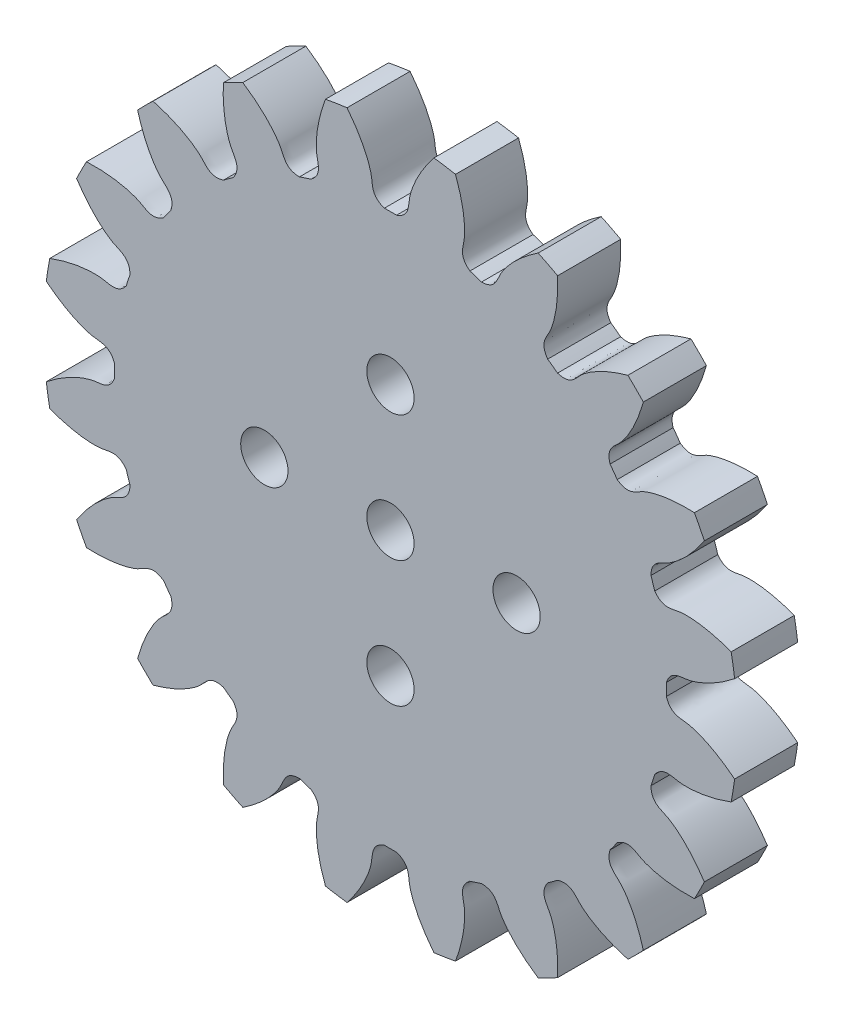
SolidWorks part; units mm, degrees
material "Thornel Mat VMA"
ref_plane "前视基准面" through (0, 0, 0) normal (0, 0, 1) x (1, 0, 0)
ref_plane "上视基准面" through (0, 0, 0) normal (0, 1, 0) x (1, 0, 0)
ref_plane "右视基准面" through (0, 0, 0) normal (1, 0, 0) x (0, 0, -1)
other "Configuration Table"
sketch "草图1" plane through (0, 0, 0) normal (0, 0, 1) x (1, 0, 0)
  circle A0 centre (0, 0) radius 22
extrude "凸台-拉伸1" add sketch "草图1" along normal blind 4
ref_axis "基准轴1" through (0, 0, -1.5) along (0, 0, 1)
sketch "草图2" plane through (0, 0, 0) normal (0, 0, 1) x (1, 0, 0)
  line L0 (0, 0) -> (0, 22) construction
  circle A0 centre (0, 0) radius 22 construction
  arc A1 (0.3866, 17.4957) -> (-0.3866, 17.4957) centre (0, 0) ccw
  arc A2 (6.3623, 24.9965) -> (-6.3623, 24.9965) centre (0, 0) ccw
  spline S0 degree 3 poles (0.3866, 17.4957) (1.2224, 17.787) (1.1142, 18.3742) (1.2258, 18.94) (1.2378, 18.9951) (1.2526, 19.0573) (1.2706, 19.1264) (1.292, 19.2024) (1.317, 19.2851) (1.3461, 19.3745) (1.3793, 19.4704) (1.4171, 19.5726) (1.4597, 19.6811) (1.5073, 19.7956) (1.5603, 19.9161) (1.6187, 20.0423) (1.683, 20.174) (1.7534, 20.3112) (1.83, 20.4535) (1.9132, 20.6008) (2.0031, 20.7529) (2.1, 20.9095) (2.204, 21.0705) (2.3155, 21.2356) (2.4346, 21.4046) (2.5615, 21.5772) (2.6964, 21.7533) (2.8395, 21.9324) (2.991, 22.1145) (3.1509, 22.2992) (3.3196, 22.4862) (3.4971, 22.6753) (3.6837, 22.8662) (3.8793, 23.0586) (4.0843, 23.2521) (4.2986, 23.4467) (4.5225, 23.6418) (4.7559, 23.8372) (4.9991, 24.0327) (5.2521, 24.2278) (5.515, 24.4223) (5.8829, 24.6833) (6.1679, 24.8727) (6.3623, 24.9965) knots 0 0 0 0 0.165916 0.170906 0.176664 0.183189 0.190482 0.198542 0.207371 0.216967 0.22733 0.238462 0.250361 0.263027 0.276462 0.290664 0.305634 0.321371 0.337876 0.355149 0.37319 0.391998 0.411574 0.431917 0.453028 0.474907 0.497554 0.520968 0.54515 0.570099 0.595817 0.622302 0.649554 0.677575 0.706363 0.735918 0.766242 0.797333 0.829191 0.861818 0.895212 0.929373 1 1 1 1
  spline S1 degree 3 poles (-0.3866, 17.4957) (-1.2224, 17.787) (-1.1142, 18.3742) (-1.2258, 18.94) (-1.2378, 18.9951) (-1.2526, 19.0573) (-1.2706, 19.1264) (-1.292, 19.2024) (-1.317, 19.2851) (-1.3461, 19.3745) (-1.3793, 19.4704) (-1.4171, 19.5726) (-1.4597, 19.6811) (-1.5073, 19.7956) (-1.5603, 19.9161) (-1.6187, 20.0423) (-1.683, 20.174) (-1.7534, 20.3112) (-1.83, 20.4535) (-1.9132, 20.6008) (-2.0031, 20.7529) (-2.1, 20.9095) (-2.204, 21.0705) (-2.3155, 21.2356) (-2.4346, 21.4046) (-2.5615, 21.5772) (-2.6964, 21.7533) (-2.8395, 21.9324) (-2.991, 22.1145) (-3.1509, 22.2992) (-3.3196, 22.4862) (-3.4971, 22.6753) (-3.6837, 22.8662) (-3.8793, 23.0586) (-4.0843, 23.2521) (-4.2986, 23.4467) (-4.5225, 23.6418) (-4.7559, 23.8372) (-4.9991, 24.0327) (-5.2521, 24.2278) (-5.515, 24.4223) (-5.8829, 24.6833) (-6.1679, 24.8727) (-6.3623, 24.9965) knots 0 0 0 0 0.165916 0.170906 0.176664 0.183189 0.190482 0.198542 0.207371 0.216967 0.22733 0.238462 0.250361 0.263027 0.276462 0.290664 0.305634 0.321371 0.337876 0.355149 0.37319 0.391998 0.411574 0.431917 0.453028 0.474907 0.497554 0.520968 0.54515 0.570099 0.595817 0.622302 0.649554 0.677575 0.706363 0.735918 0.766242 0.797333 0.829191 0.861818 0.895212 0.929373 1 1 1 1
extrude "切除-拉伸1" cut sketch "草图2" along normal through all
pattern_circular "阵列(圆周)1" count 20 every 18 about axis through (0, 0, -1.5) along (0, 0, 1) of "切除-拉伸1"
sketch "草图3" plane through (0, 0, 0) normal (0, 0, 1) x (1, 0, 0)
  circle A0 centre (0, 0) radius 20 construction
  dimension "Dn" = 40
sketch "草图4" plane through (0, 0, 4) normal (0, 0, 1) x (1, 0, 0)
  line L0 (0, 0) -> (0, 33.3551) construction
  line L1 (0, 0) -> (47.7398, 0) construction
  circle A0 centre (0, 8) radius 1.5
  circle A1 centre (8, 0) radius 1.5
  circle A2 centre (-8, 0) radius 1.5
  circle A3 centre (0, -8) radius 1.5
  circle A4 centre (0, 0) radius 1.5
  dimension "D1" = 3
  dimension "D2" = 3
  dimension "D3" = 16
  dimension "D4" = 16
  dimension "D5" = 3
extrude "切除-拉伸2" cut sketch "草图4" against normal blind 10
